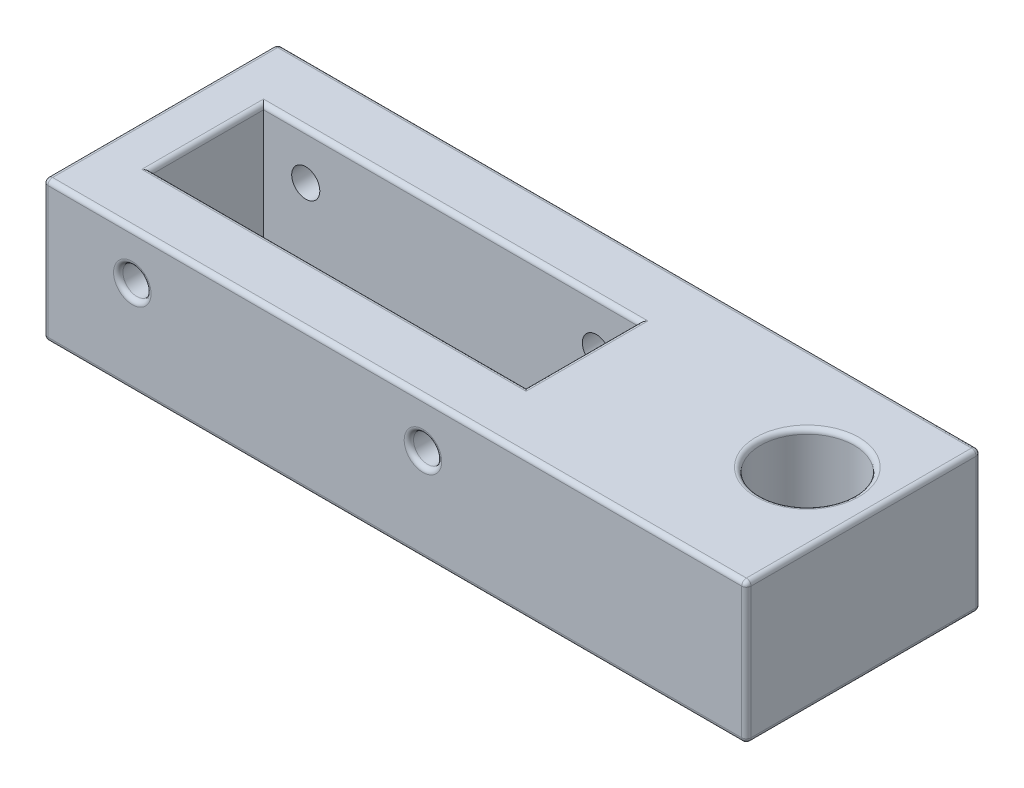
SolidWorks part; units mm, degrees
material "1060 Alloy"
ref_plane "Front Plane" through (0, 0, 0) normal (0, 0, 1) x (1, 0, 0)
ref_plane "Top Plane" through (0, 0, 0) normal (0, 1, 0) x (1, 0, 0)
ref_plane "Right Plane" through (0, 0, 0) normal (1, 0, 0) x (0, 0, -1)
sketch "Sketch1" plane through (0, 0, 0) normal (0, 1, 0) x (1, 0, 0)
  line L1 (750, 250) -> (-750, 250)
  line L2 (750, 250) -> (750, -250)
  line L3 (750, -250) -> (-750, -250)
  line L4 (-750, 250) -> (-750, -250)
  point P0 (0, 0)
  dimension "D1" = 500
  dimension "D2" = 1500
extrude "Boss-Extrude6" add sketch "Sketch1" along normal blind 300
sketch "Sketch4" plane through (0, 0, 250) normal (0, 0, 1) x (1, 0, 0)
  line L0 (-750, 300) -> (-750, 0) construction
  circle A0 centre (-560, 200) radius 30
  circle A1 centre (60, 200) radius 30
  dimension "D3" = 60
  dimension "D4" = 60
  dimension "D1" = 190
  dimension "D2" = 620
extrude "Cut-Extrude3" cut sketch "Sketch4" against normal through all both and the other way through all
sketch "Sketch6" plane through (0, 300, 0) normal (0, 1, 0) x (1, 0, 0)
  line L0 (750, 250) -> (-750, 250) construction
  line L1 (-650, 120) -> (150, 120)
  line L2 (-650, 120) -> (-650, -120)
  line L3 (-650, -120) -> (150, -120)
  line L4 (150, 120) -> (150, -120)
  line L5 (-650, 120) -> (150, -120) construction
  line L6 (-650, -120) -> (150, 120) construction
  line L7 (-750, 250) -> (-750, -250) construction
  line L8 (750, -250) -> (750, 250) construction
  circle A0 centre (600, 30) radius 100
  point P0 (-250, 0)
  point P9 (-750, 0)
  dimension "D6" = 200
  dimension "D7" = 220
  dimension "D1" = 240
  dimension "D2" = 250
  dimension "D3" = 800
  dimension "D4" = 100
  dimension "D5" = 150
fillet "Fillet1" radius 10 4 edges at (0, 0, 250) (750, 0, 0) (0, 0, -250) (-750, 0, 0)
fillet "Fillet3" radius 10 5 edges at (-747.0711, 2.9289, -247.0711) (747.0711, 2.9289, -247.0711) (0, 300, -250) (-750, 155, -250) (750, 155, -250)
fillet "Fillet4" radius 10 2 edges at (90, 200, -250) (-530, 200, -250)
fillet "Fillet5" radius 10 2 edges at (-590, 200, 250) (30, 200, 250)
fillet "Fillet6" radius 10 5 edges at (747.0711, 2.9289, 247.0711) (-747.0711, 2.9289, 247.0711) (0, 300, 250) (750, 155, 250) (-750, 155, 250)
fillet "Fillet7" radius 10 6 edges at (747.0711, 297.0711, -247.0711) (750, 300, 0) (-747.0711, 297.0711, -247.0711) (-750, 300, 0) (747.0711, 297.0711, 247.0711) (-747.0711, 297.0711, 247.0711)
extrude "Cut-Extrude6" cut sketch "Sketch6" against normal through all both and the other way through all contours A0 | L2 L3 L4 L1
fillet "Fillet8" radius 10 5 edges at (600, 300, -130) (-650, 300, 0) (-250, 300, 120) (150, 300, 0) (-250, 300, -120)
fillet "Fillet9" radius 10 5 edges at (600, 0, 70) (-250, 0, 120) (-650, 0, 0) (-250, 0, -120) (150, 0, 0)
